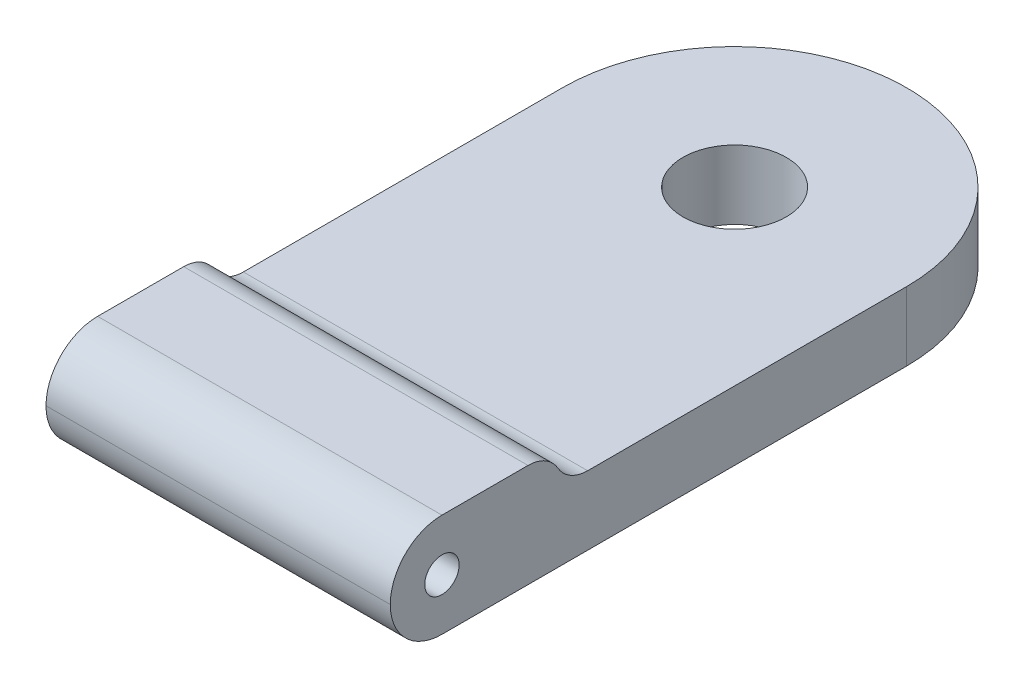
SolidWorks part; units mm, degrees
ref_plane "Alzado" through (0, 0, 0) normal (0, 0, 1) x (1, 0, 0)
ref_plane "Planta" through (0, 0, 0) normal (0, 1, 0) x (1, 0, 0)
ref_plane "Vista lateral" through (0, 0, 0) normal (1, 0, 0) x (0, 0, -1)
sketch "Croquis1" plane through (0, 0, 0) normal (0, 1, 0) x (1, 0, 0)
  line L1 (0, 0) -> (10, 0)
  line L2 (0, 0) -> (0, 15)
  line L4 (10, 0) -> (10, 15)
  arc A1 (10, 15) -> (0, 15) centre (5, 15) ccw
  point P0 (0, 0)
  dimension "D1" = 15
  dimension "D2" = 10
extrude "Saliente-Extruir1" add sketch "Croquis1" along normal blind 3
sketch "Croquis3" plane through (0, 0, 0) normal (1, 0, 0) x (0, 0, -1)
  line L0 (0, 3) -> (15, 3) construction
  line L1 (5, 3) -> (20, 3)
  line L2 (5, 3) -> (5, 2)
  line L3 (5, 2) -> (20, 2)
  line L4 (20, 3) -> (20, 2)
  line L6 (0, 3) -> (0, 0) construction
  dimension "D1" = 15
  dimension "D2" = 1
  dimension "D3" = 5
extrude "Cortar-Extruir1" cut sketch "Croquis3" along normal up to surface (10 mm away) up to face at (10, 1.5, -7.5)
fillet "Redondeo1" radius 1 1 edges at (5, 3, -5)
fillet "Redondeo3" radius 1 1 edges at (5, 2, -5)
sketch "Croquis4" plane through (10, 0, 0) normal (1, 0, 0) x (0, 0, -1)
  line L0 (0, 3) -> (4, 3) construction
  line L1 (0, 3) -> (0, 0) construction
  circle A0 centre (1.5, 1.5) radius 0.5
  dimension "D1" = 1
  dimension "D2" = 1.5
  dimension "D3" = 1.5
extrude "Cortar-Extruir2" cut sketch "Croquis4" against normal up to surface (10 mm away) up to face at (0, 1.7857, -6.3712)
fillet "Redondeo4" radius 1.5 1 edges at (5, 3, 0)
fillet "Redondeo5" radius 1.5 1 edges at (5, 0, 0)
sketch "Croquis5" plane through (0, 2, 0) normal (0, 1, 0) x (1, 0, 0)
  circle A2 centre (5, 15) radius 1.5
  dimension "D1" = 3
extrude "Cortar-Extruir3" cut sketch "Croquis5" against normal blind 3
